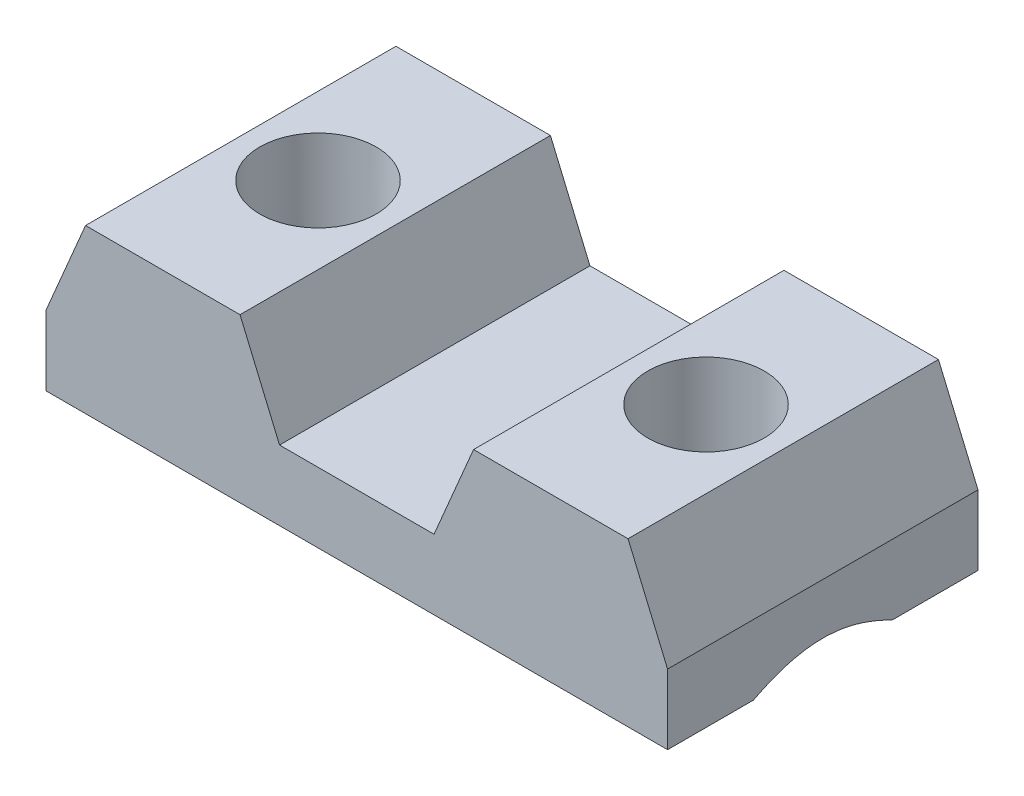
SolidWorks part; units mm, degrees
material "ABS"
ref_plane "正面" through (0, 0, 0) normal (0, 0, 1) x (1, 0, 0)
ref_plane "平面" through (0, 0, 0) normal (0, 1, 0) x (1, 0, 0)
ref_plane "右側面" through (0, 0, 0) normal (1, 0, 0) x (0, 0, -1)
sketch "ｽｹｯﾁ1" plane through (0, 0, 0) normal (0, 0, 1) x (1, 0, 0)
  line L0 (-6.9906, 0) -> (-3.0094, 0)
  line L1 (-3.0094, 0) -> (-1.9906, -2.4)
  line L2 (-1.9906, -2.4) -> (1.9906, -2.4)
  line L3 (0, 0) -> (0, -4.2434) construction
  line L4 (3.0094, 0) -> (1.9906, -2.4)
  line L5 (6.9906, 0) -> (3.0094, 0)
  line L6 (-5, 0) -> (-5, -1.6451) construction
  line L7 (5, 0) -> (5, -1.6451) construction
  line L8 (-6.9906, 0) -> (-8.0094, -2.4)
  line L9 (6.9906, 0) -> (8.0094, -2.4)
  line L17 (-1.5, -2.4) -> (-3, -3.9) construction
  line L18 (-3, -3.9) -> (-3, -4.2) construction
  line L19 (-3, -4.2) -> (3, -4.2) construction
  line L20 (-8.0094, -2.4) -> (-8.0094, -4.2)
  line L21 (3, -3.9) -> (3, -4.2) construction
  line L22 (1.5, -2.4) -> (3, -3.9) construction
  line L23 (-8.0094, -4.2) -> (8.0094, -4.2)
  line L24 (8.0094, -4.2) -> (8.0094, -2.4)
  point P8 (0, -2.4)
  point P16 (-5, 0)
  point P18 (5, 0)
  dimension "D1" = 2.4
  dimension "D2" = 10
  dimension "D3" = 23
  dimension "D4" = 3
  dimension "D5" = 6
  dimension "D6" = 1.8
extrude "ﾎﾞｽ - 押し出し1" add sketch "ｽｹｯﾁ1" along normal blind 8
sketch "ｽｹｯﾁ2" plane through (0, 0, 0) normal (0, 1, 0) x (1, 0, 0)
  line L0 (-6.9906, -4) -> (6.9906, -4) construction
  line L1 (-6.9906, -8) -> (-6.9906, 0) construction
  line L2 (6.9906, -8) -> (6.9906, 0) construction
  circle A0 centre (-5, -4) radius 1.5
  circle A1 centre (5, -4) radius 1.5
  dimension "D1" = 3
  dimension "D2" = 10
  dimension "D3" = 5
extrude "ｶｯﾄ - 押し出し1" cut sketch "ｽｹｯﾁ2" against normal through all
chamfer "面取り1" distance 2 angle 45 2 edges at (-6.5, -4.2, 4) (3.5, -4.2, 4)
